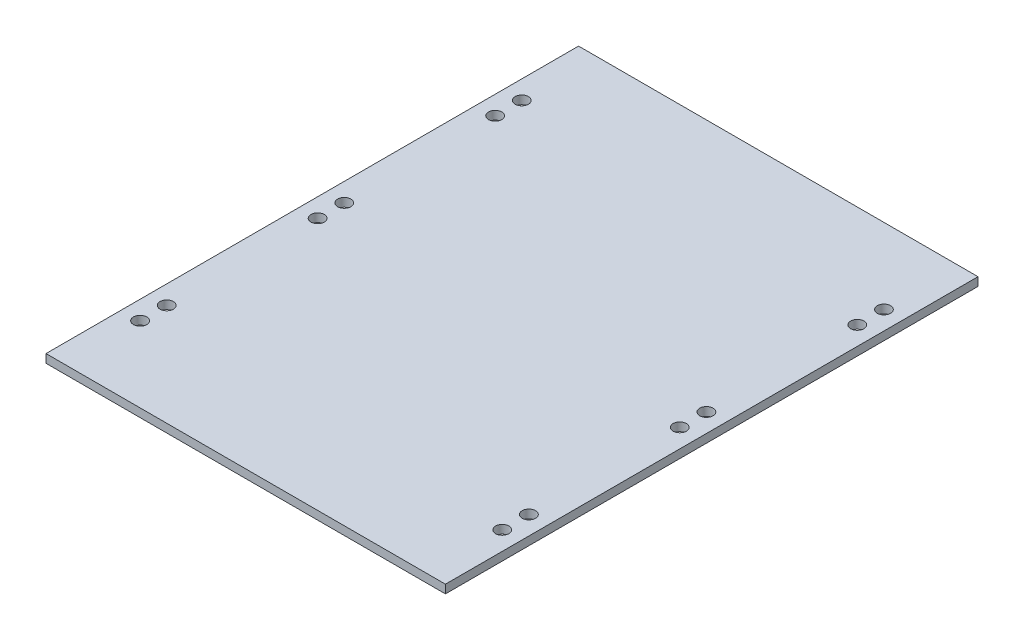
SolidWorks part; units mm, degrees
ref_plane "Front Plane" through (0, 0, 0) normal (0, 0, 1) x (1, 0, 0)
ref_plane "Top Plane" through (0, 0, 0) normal (0, 1, 0) x (1, 0, 0)
ref_plane "Right Plane" through (0, 0, 0) normal (1, 0, 0) x (0, 0, -1)
sketch "Sketch1" plane through (0, 0, 0) normal (0, 1, 0) x (1, 0, 0)
  line L0 (0, 100) -> (0, -100) construction
  line L1 (-75, 100) -> (75, 100)
  line L2 (-75, 100) -> (-75, -100)
  line L3 (-75, -100) -> (75, -100)
  line L4 (75, 100) -> (75, -100)
  line L5 (-75, 100) -> (75, -100) construction
  line L6 (-75, -100) -> (75, 100) construction
  line L7 (-75, 33.3333) -> (75, 33.3333) construction
  line L8 (-75, -33.3333) -> (75, -33.3333) construction
  circle A0 centre (-68, -61.6667) radius 2.5
  circle A1 centre (-68, -71.6667) radius 2.5
  circle A2 centre (-68, 5) radius 2.5
  circle A3 centre (-68, -5) radius 2.5
  circle A4 centre (-68, 71.6667) radius 2.5
  circle A5 centre (-68, 61.6667) radius 2.5
  circle A6 centre (68, 61.6667) radius 2.5
  circle A7 centre (68, 71.6667) radius 2.5
  circle A8 centre (68, -5) radius 2.5
  circle A9 centre (68, 5) radius 2.5
  circle A10 centre (68, -71.6667) radius 2.5
  circle A11 centre (68, -61.6667) radius 2.5
  point P0 (0, 0)
  dimension "D5" = 5
  dimension "D1" = 200
  dimension "D2" = 66.6667
  dimension "D3" = 66.6667
  dimension "D4" = 66.6667
  dimension "D6" = 10
  dimension "D7" = 7
  dimension "D8" = 28.3333
  dimension "D9" = 150
extrude "Boss-Extrude1" add sketch "Sketch1" along normal blind 3.175
equation "\"D2@Sketch1\"=\"D1@Sketch1\"/3"
equation "\"D3@Sketch1\"=\"D1@Sketch1\"/3"
equation "\"D8@Sketch1\"=(\"D3@Sketch1\"-\"D6@Sketch1\")/2"
